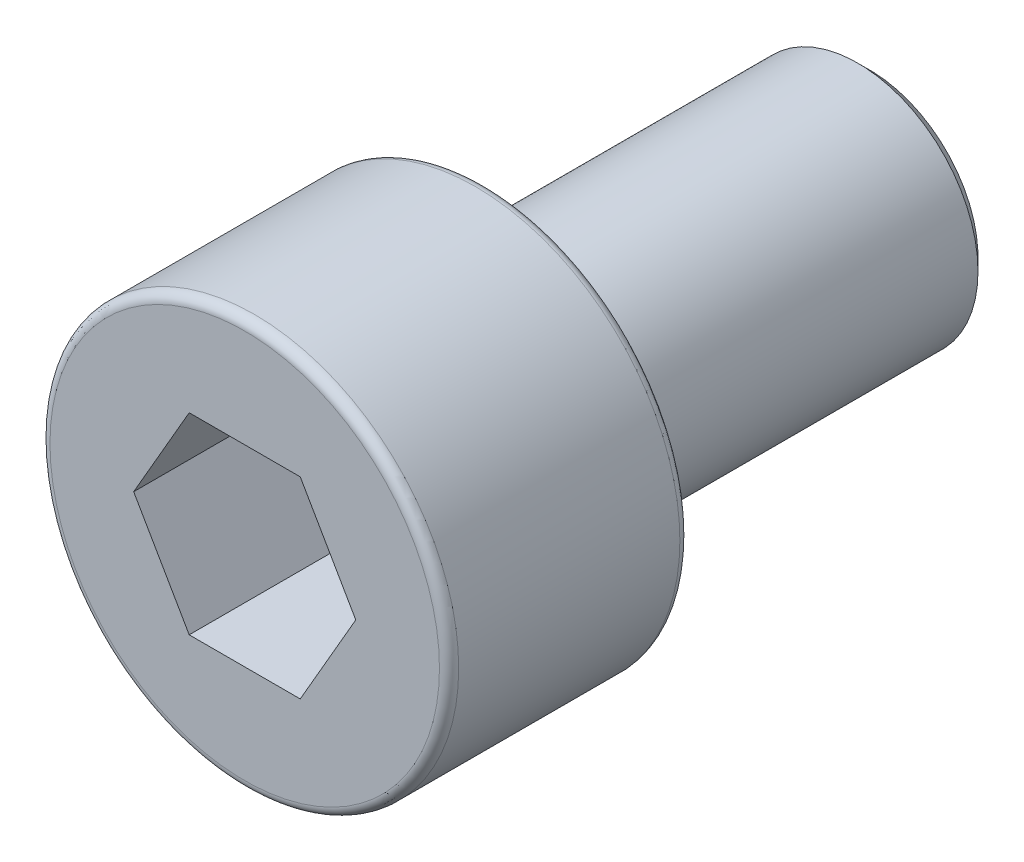
SolidWorks part; units mm, degrees
ref_plane "Front Plane" through (0, 0, 0) normal (0, 0, 1) x (1, 0, 0)
ref_plane "Top Plane" through (0, 0, 0) normal (0, 1, 0) x (1, 0, 0)
ref_plane "Right Plane" through (0, 0, 0) normal (1, 0, 0) x (0, 0, -1)
ref_plane "Plane1" through (0, 0, 13) normal (0, 0, 1) x (1, 0, 0)
sketch "Sketch1" plane through (0, 0, 13) normal (0, 0, 1) x (1, 0, 0)
  circle A0 centre (0, 0) radius 4.25
extrude "Boss-Extrude1" add sketch "Sketch1" against normal blind 5
sketch "Sketch2" plane through (0, 0, 8) normal (0, 0, -1) x (-1, 0, 0)
  circle A0 centre (0, 0) radius 2.5
extrude "Boss-Extrude2" add sketch "Sketch2" along normal blind 8
sketch "Sketch3" plane through (0, 0, 13) normal (0, 0, 1) x (1, 0, 0)
  line L0 (-2.3094, 0) -> (-1.1547, -2)
  line L1 (-1.1547, -2) -> (1.1547, -2)
  line L2 (1.1547, -2) -> (2.3094, 0)
  line L3 (2.3094, 0) -> (1.1547, 2)
  line L4 (1.1547, 2) -> (-1.1547, 2)
  line L5 (-1.1547, 2) -> (-2.3094, 0)
extrude "Cut-Extrude1" cut sketch "Sketch3" against normal blind 4
chamfer "Chamfer1" distance 0.25 angle 45 1 edges at (-2.5, 0, 0)
fillet "Fillet1" radius 0.2 2 edges at (-4.25, 0, 8) (-4.25, 0, 13) tangent propagation no
ref_axis "Axis1" through (0, 0, -1.9217) along (0, 0, 1)
